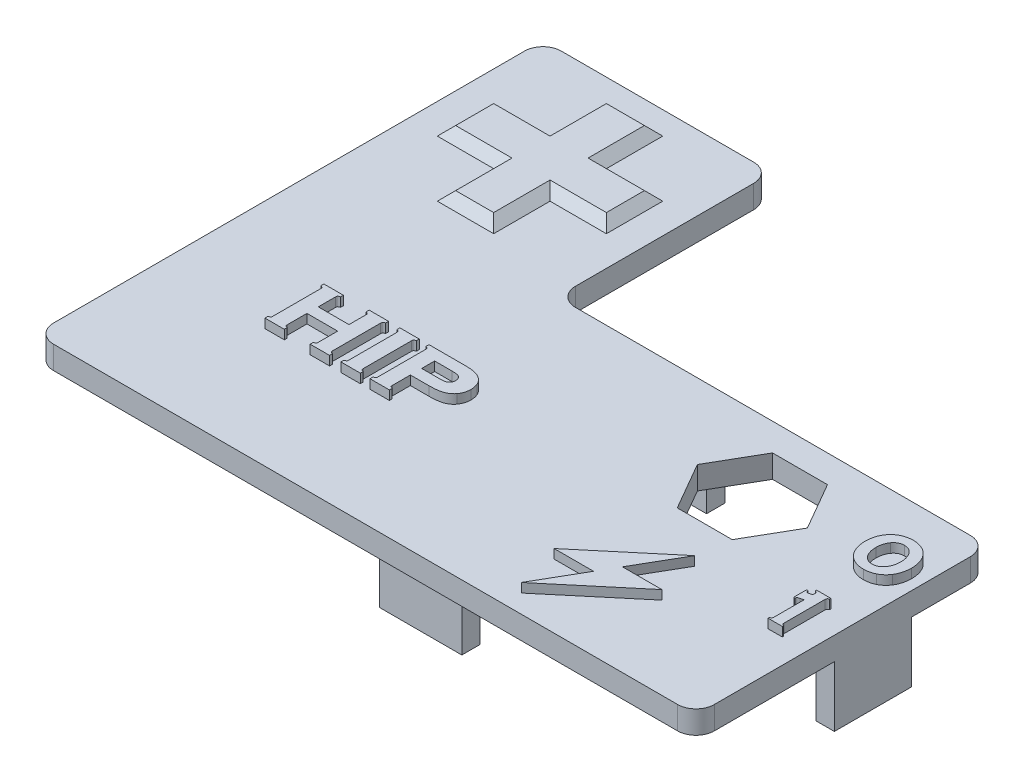
SolidWorks part; units mm, degrees
ref_plane "Front" through (0, 0, 0) normal (0, 0, 1) x (1, 0, 0)
ref_plane "Top" through (0, 0, 0) normal (0, 1, 0) x (1, 0, 0)
ref_plane "Right" through (0, 0, 0) normal (1, 0, 0) x (0, 0, -1)
sketch "Sketch1" plane through (0, 0, 0) normal (0, 1, 0) x (1, 0, 0)
  line L0 (-36.05, 15.975) -> (-36.05, 39.425)
  line L1 (-36.05, -15.975) -> (36.05, -15.975)
  line L2 (-36.05, -15.975) -> (-36.05, 15.975)
  line L3 (-11.05, 15.975) -> (36.05, 15.975)
  line L4 (36.05, -15.975) -> (36.05, 15.975)
  line L5 (-36.05, -15.975) -> (36.05, 15.975) construction
  line L6 (-36.05, 15.975) -> (36.05, -15.975) construction
  line L7 (-36.05, 39.425) -> (-11.05, 39.425)
  line L8 (-11.05, 39.425) -> (-11.05, 15.975)
  point P0 (0, 0)
  dimension "D1" = 31.95
  dimension "D2" = 72.1
  dimension "D3" = 25
  dimension "D4" = 55.4
extrude "Boss-Extrude1" add sketch "Sketch1" along normal blind 2.5
fillet "Fillet1" radius 2 6 edges at (36.05, 1.25, -15.975) (36.05, 1.25, 15.975) (-36.05, 1.25, 15.975) (-11.05, 1.25, -15.975) (-11.05, 1.25, -39.425) (-36.05, 1.25, -39.425)
sketch "Sketch2" plane through (0, 0, 0) normal (0, -1, 0) x (1, 0, 0)
  line L0 (36.05, 13.975) -> (36.05, -13.975) construction
  line L1 (34.05, -7.525) -> (36.05, -7.525)
  line L2 (34.05, -7.525) -> (34.05, 0.875)
  line L3 (34.05, 0.875) -> (36.05, 0.875)
  line L4 (36.05, -7.525) -> (36.05, 0.875)
  line L5 (34.05, -7.525) -> (36.05, 0.875) construction
  line L6 (34.05, 0.875) -> (36.05, -7.525) construction
  line L7 (35.05, -7.575) -> (35.05, 0.925) construction
  line L8 (35.05, 0.925) -> (35.05, 15.975) construction
  line L9 (-34.05, 15.975) -> (34.05, 15.975) construction
  line L10 (34.05, -15.975) -> (-9.05, -15.975) construction
  line L11 (8.5, -14.725) -> (-0.5, -14.725)
  line L12 (8.5, -14.725) -> (8.5, -12.725)
  line L13 (8.5, -12.725) -> (-0.5, -12.725)
  line L14 (-0.5, -14.725) -> (-0.5, -12.725)
  line L15 (8.5, -14.725) -> (-0.5, -12.725) construction
  line L16 (8.5, -12.725) -> (-0.5, -14.725) construction
  line L17 (8.5, 11.975) -> (-0.5, 11.975)
  line L18 (8.5, 11.975) -> (8.5, 13.975)
  line L19 (8.5, 13.975) -> (-0.5, 13.975)
  line L20 (-0.5, 11.975) -> (-0.5, 13.975)
  line L21 (8.5, 11.975) -> (-0.5, 13.975) construction
  line L22 (8.5, 13.975) -> (-0.5, 11.975) construction
  line L23 (0, 0) -> (-50000, 0) construction
  point P0 (35.05, -3.325)
  point P7 (35.05, -3.325)
  point P13 (4, -13.725)
  point P18 (4, 12.975)
  dimension "D1" = 2
  dimension "D2" = 8.4
  dimension "D3" = 15.05
  dimension "D4" = 8.5
  dimension "D5" = 2
  dimension "D6" = 1.25
  dimension "D7" = 2
  dimension "D8" = 0.5
  dimension "D9" = 9
extrude "Boss-Extrude2" add sketch "Sketch2" along normal blind 6.6
sketch "Sketch3" plane through (0, 2.5, 0) normal (0, 1, 0) x (1, 0, 0)
  line L0 (-22.8, 6.025) -> (-7.8, 6.025) construction
  line L1 (-34.05, -2.975) -> (3.45, -2.975) construction
  line L2 (29.55, 6.025) -> (36.05, 6.025) construction
  line L9 (21.9141, -1.975) -> (19.0274, -6.975)
  line L11 (17.8726, -8.975) -> (14.9859, -13.975)
  line L12 (14.9859, -13.975) -> (23.3282, -6.975)
  line L13 (23.3282, -6.975) -> (19.0274, -6.975)
  line L14 (21.9141, -1.975) -> (13.5718, -8.975)
  line L15 (13.5718, -8.975) -> (17.8726, -8.975)
  line L16 (12.7, -15.975) -> (12.7, 0.025) construction
  line L17 (-34.05, -15.975) -> (34.05, -15.975) construction
  line L18 (12.7, 0.025) -> (24.2, 0.025) construction
  line L19 (24.2, 0.025) -> (24.2, -15.975) construction
  line L20 (24.2, -15.975) -> (12.7, -15.975) construction
  line L21 (36.05, -13.975) -> (36.05, 13.975) construction
  line L22 (21.9141, -1.975) -> (14.9859, -13.975) construction
  line L23 (-26.625, 36.925) -> (-20.475, 36.925)
  line L24 (-20.475, 36.925) -> (-20.475, 30.775)
  line L25 (-36.05, 37.425) -> (-36.05, -13.975) construction
  line L26 (-20.475, 30.775) -> (-14.325, 30.775)
  line L27 (-14.325, 30.775) -> (-14.325, 24.625)
  line L28 (-14.325, 24.625) -> (-20.475, 24.625)
  line L29 (-20.475, 24.625) -> (-20.475, 18.475)
  line L30 (-20.475, 18.475) -> (-26.625, 18.475)
  line L31 (-26.625, 18.475) -> (-26.625, 24.625)
  line L32 (-26.625, 24.625) -> (-32.775, 24.625)
  line L33 (-32.775, 24.625) -> (-32.775, 30.775)
  line L34 (-32.775, 30.775) -> (-26.625, 30.775)
  line L35 (-26.625, 30.775) -> (-26.625, 36.925)
  line L36 (-11.05, 27.7) -> (-36.05, 27.7) construction
  line L37 (-11.05, 17.975) -> (-11.05, 37.425) construction
  line L38 (-36.05, 37.425) -> (-36.05, -13.975) construction
  line L39 (-13.05, 39.425) -> (-34.05, 39.425) construction
  text T0 "<b>HIP</b>" font "Copperplate Gothic Bold" height 6.35
  text T2 "0\r\n1" font "Copperplate Gothic Bold" height in points 26
  point P18 (18.45, -7.975)
  point P19 (18.45, 0.025)
  point P20 (12.7, -7.975)
  point P38 (-32.775, 27.7)
  point P43 (-15.3, 6.025)
  point P44 (-15.3, -2.975)
  point P50 (-23.55, 36.925)
  point P51 (-23.55, 27.7)
  dimension "D1" = 40
  dimension "D2" = 20
  dimension "D3" = 2
  dimension "D4" = 5
  dimension "D5" = 11.85
  dimension "D6" = 23.35
  dimension "D7" = 2
  dimension "D8" = 6.5
  dimension "D9" = 22
  dimension "D10" = 22
  dimension "D11" = 2
  dimension "D12" = 9
  dimension "D13" = 37.5
  dimension "D14" = 15
  dimension "D15" = 2.5
extrude "Boss-Extrude3" add sketch "Sketch3" along normal blind 1
sketch "Sketch4" plane through (0, 2.5, 0) normal (0, 1, 0) x (1, 0, 0)
  line L5 (34.05, 15.975) -> (-9.05, 15.975) construction
  line L7 (18.45, 2.5827) -> (18.45, -15.975) construction
  line L9 (21.45, 2.5827) -> (24.45, 7.7788)
  line L10 (24.45, 7.7788) -> (21.45, 12.975)
  line L11 (21.45, 12.975) -> (15.45, 12.975)
  line L12 (15.45, 12.975) -> (12.45, 7.7788)
  line L13 (12.45, 7.7788) -> (15.45, 2.5827)
  line L14 (15.45, 2.5827) -> (21.45, 2.5827)
  line L15 (24.2, -15.975) -> (12.7, -15.975) construction
  circle A0 centre (18.45, 7.7788) radius 5.1962 construction
  dimension "D1" = 3
  dimension "D2" = 6
extrude "Cut-Extrude1" cut sketch "Sketch4" against normal up to vertex (2.5 mm away) up to point (34.05, 0, 15.975)
chamfer "Chamfer1" distance 1 angle 45 12 edges at (-23.55, 3.5, -36.925) (-20.475, 3.5, -33.85) (-17.4, 3.5, -30.775) (-14.325, 3.5, -27.7) (-17.4, 3.5, -24.625) (-20.475, 3.5, -21.55) (-23.55, 3.5, -18.475) (-26.625, 3.5, -21.55) (-29.7, 3.5, -24.625) (-32.775, 3.5, -27.7) (-29.7, 3.5, -30.775) (-26.625, 3.5, -33.85)
